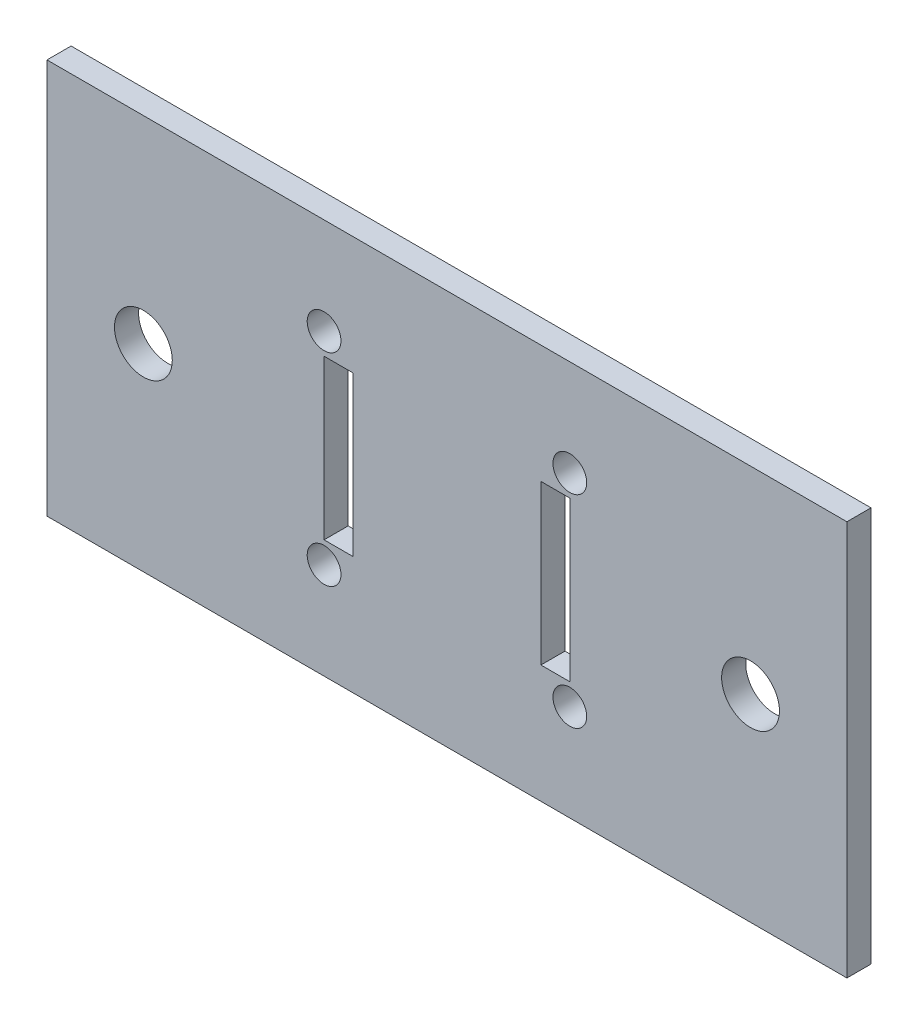
SolidWorks part; units mm, degrees
ref_plane "Front Plane" through (0, 0, 0) normal (0, 0, 1) x (1, 0, 0)
ref_plane "Top Plane" through (0, 0, 0) normal (0, 1, 0) x (1, 0, 0)
ref_plane "Right Plane" through (0, 0, 0) normal (1, 0, 0) x (0, 0, -1)
sketch "Sketch1" plane through (0, 0, 0) normal (0, 0, 1) x (1, 0, 0)
  line L0 (-31.5, 0) -> (31.5, 0) construction
  line L1 (-41.5, 20.5) -> (41.5, 20.5)
  line L2 (-41.5, 20.5) -> (-41.5, -20.5)
  line L3 (-41.5, -20.5) -> (41.5, -20.5)
  line L4 (41.5, 20.5) -> (41.5, -20.5)
  line L5 (-41.5, 20.5) -> (41.5, -20.5) construction
  line L6 (-41.5, -20.5) -> (41.5, 20.5) construction
  line L8 (-12.75, -10.5) -> (12.75, -10.5) construction
  line L9 (-12.75, -10.5) -> (-12.75, 10.5) construction
  line L10 (-12.75, 10.5) -> (12.75, 10.5) construction
  line L11 (12.75, -10.5) -> (12.75, 10.5) construction
  line L12 (-12.75, -10.5) -> (12.75, 10.5) construction
  line L13 (-12.75, 10.5) -> (12.75, -10.5) construction
  line L14 (-12.75, 8.25) -> (-9.75, 8.25)
  line L15 (-12.75, 8.25) -> (-12.75, -8.25)
  line L16 (-12.75, -8.25) -> (-9.75, -8.25)
  line L17 (-9.75, 8.25) -> (-9.75, -8.25)
  line L18 (12.75, 8.25) -> (9.75, 8.25)
  line L19 (12.75, 8.25) -> (12.75, -8.25)
  line L20 (12.75, -8.25) -> (9.75, -8.25)
  line L21 (9.75, 8.25) -> (9.75, -8.25)
  circle A0 centre (-31.5, 0) radius 3
  circle A1 centre (31.5, 0) radius 3
  circle A2 centre (-12.75, 10.5) radius 1.75
  circle A3 centre (12.75, 10.5) radius 1.75
  circle A4 centre (12.75, -10.5) radius 1.75
  circle A5 centre (-12.75, -10.5) radius 1.75
  point P0 (0, 0)
  point P10 (0, 0)
  point P27 (-9.75, 0)
  dimension "D2" = 6
  dimension "D7" = 3.5
  dimension "D1" = 10
  dimension "D3" = 21
  dimension "D4" = 25.5
  dimension "D5" = 31.5
  dimension "D6" = 10
  dimension "D8" = 16.5
  dimension "D9" = 3
extrude "Boss-Extrude1" add sketch "Sketch1" along normal blind 2.5
